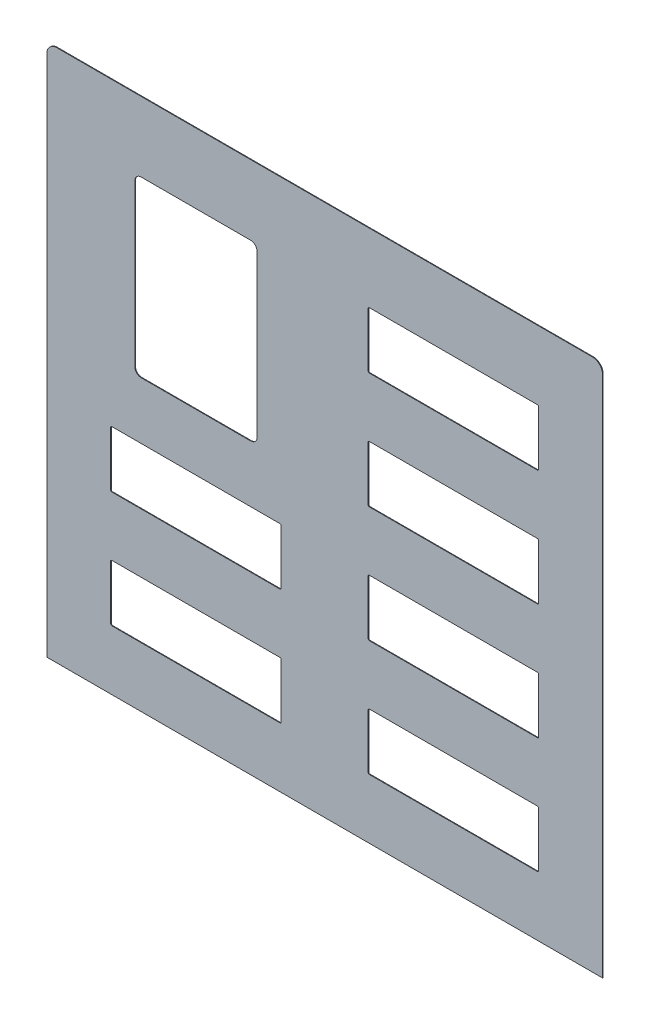
SolidWorks part; units mm, degrees
ref_plane "Front Plane" through (0, 0, 0) normal (0, 0, 1) x (1, 0, 0)
ref_plane "Top Plane" through (0, 0, 0) normal (0, 1, 0) x (1, 0, 0)
ref_plane "Right Plane" through (0, 0, 0) normal (1, 0, 0) x (0, 0, -1)
sketch "Sketch1" plane through (0, 0, 0) normal (0, 0, 1) x (1, 0, 0)
  line L1 (0, 0) -> (863.4, 0)
  line L2 (0, 0) -> (0, 812)
  line L3 (15.7, 827.7) -> (847.7, 827.7)
  line L4 (863.4, 0) -> (863.4, 812)
  arc A0 (847.7, 827.7) -> (863.4, 812) centre (847.7, 812) cw
  arc A1 (0, 812) -> (15.7, 827.7) centre (15.7, 812) cw
  dimension "D3" = 15.7
  dimension "D1" = 863.4
  dimension "D2" = 827.7
base flange "Base-Flange1" sketch "Sketch1" thickness 1 reverse thickness direction no parameters "D1"=1
edge flange "Edge-Flange1" [suppressed] sketch "Sketch8" flange angle 90 flange position material inside bend radius 1 thickness 1
sketch "Sketch8" plane through (0, 0, -1) normal (0, -1, 0) x (-1, 0, 0)
  line L0 (0, 0) -> (-822, 0) construction
  line L1 (-42, 0) -> (-780, 0)
  line L2 (-780, 0) -> (-780, 12)
  line L3 (-780, 12) -> (-42, 12)
  line L4 (-42, 12) -> (-42, 0)
  line L5 (0, 0) -> (0, -1) construction
  line L6 (-822, 0) -> (-822, -1) construction
  circle A0 centre (-81, 6) radius 2.75
  circle A1 centre (-261, 6) radius 2.75
  circle A2 centre (-441, 6) radius 2.75
  circle A3 centre (-621, 6) radius 2.75
  circle A4 centre (-801, 6) radius 2.75
  circle A5 centre (-981, 6) radius 2.75
  circle A6 centre (-1161, 6) radius 2.75
  point P6 (-42, 6)
  dimension "D1" = 5.5
  dimension "D2" = 39
  dimension "D4" = 42
  dimension "D5" = 42
  dimension "D3" = 7
bend "EdgeBend1" bend radius 1 bend angle 90 parameters "D5"=1, "D6"=10, "D7"=12
sketch "Sketch9" plane through (0, 0, 0) normal (0, 0, 1) x (1, 0, 0)
  line L0 (863.4, 0) -> (863.4, 812) construction
  line L1 (762.2, 720.7) -> (501.2, 720.7)
  line L2 (764.2, 718.7) -> (764.2, 634.7)
  line L3 (762.2, 632.7) -> (501.2, 632.7)
  line L4 (499.2, 718.7) -> (499.2, 634.7)
  line L5 (847.7, 827.7) -> (15.7, 827.7) construction
  line L38 (764.2, 538.7) -> (764.2, 454.7)
  line L39 (762.2, 540.7) -> (501.2, 540.7)
  line L40 (762.2, 452.7) -> (501.2, 452.7)
  line L41 (499.2, 538.7) -> (499.2, 454.7)
  line L42 (764.2, 358.7) -> (764.2, 274.7)
  line L43 (762.2, 360.7) -> (501.2, 360.7)
  line L44 (762.2, 272.7) -> (501.2, 272.7)
  line L45 (499.2, 358.7) -> (499.2, 274.7)
  line L46 (764.2, 178.7) -> (764.2, 94.7)
  line L47 (762.2, 180.7) -> (501.2, 180.7)
  line L48 (762.2, 92.7) -> (501.2, 92.7)
  line L49 (499.2, 178.7) -> (499.2, 94.7)
  line L58 (364.2, 358.7) -> (364.2, 274.7)
  line L59 (362.2, 360.7) -> (101.2, 360.7)
  line L60 (362.2, 272.7) -> (101.2, 272.7)
  line L61 (99.2, 358.7) -> (99.2, 274.7)
  line L62 (364.2, 178.7) -> (364.2, 94.7)
  line L63 (362.2, 180.7) -> (101.2, 180.7)
  line L64 (362.2, 92.7) -> (101.2, 92.7)
  line L65 (99.2, 178.7) -> (99.2, 94.7)
  line L66 (364.2, 718.7) -> (364.2, 634.7) [skipped]
  line L67 (362.2, 720.7) -> (101.2, 720.7) [skipped]
  line L68 (362.2, 632.7) -> (101.2, 632.7) [skipped]
  line L69 (99.2, 718.7) -> (99.2, 634.7) [skipped]
  line L70 (364.2, 538.7) -> (364.2, 454.7) [skipped]
  line L71 (362.2, 540.7) -> (101.2, 540.7) [skipped]
  line L72 (362.2, 452.7) -> (101.2, 452.7) [skipped]
  line L73 (99.2, 538.7) -> (99.2, 454.7) [skipped]
  arc A0 (764.2, 634.7) -> (762.2, 632.7) centre (762.2, 634.7) cw
  arc A1 (501.2, 632.7) -> (499.2, 634.7) centre (501.2, 634.7) cw
  arc A2 (501.2, 720.7) -> (499.2, 718.7) centre (501.2, 718.7) ccw
  arc A3 (762.2, 720.7) -> (764.2, 718.7) centre (762.2, 718.7) cw
  arc A36 (762.2, 540.7) -> (764.2, 538.7) centre (762.2, 538.7) cw
  arc A37 (764.2, 454.7) -> (762.2, 452.7) centre (762.2, 454.7) cw
  arc A38 (501.2, 452.7) -> (499.2, 454.7) centre (501.2, 454.7) cw
  arc A39 (501.2, 540.7) -> (499.2, 538.7) centre (501.2, 538.7) ccw
  arc A40 (762.2, 360.7) -> (764.2, 358.7) centre (762.2, 358.7) cw
  arc A41 (764.2, 274.7) -> (762.2, 272.7) centre (762.2, 274.7) cw
  arc A42 (501.2, 272.7) -> (499.2, 274.7) centre (501.2, 274.7) cw
  arc A43 (501.2, 360.7) -> (499.2, 358.7) centre (501.2, 358.7) ccw
  arc A44 (762.2, 180.7) -> (764.2, 178.7) centre (762.2, 178.7) cw
  arc A45 (764.2, 94.7) -> (762.2, 92.7) centre (762.2, 94.7) cw
  arc A46 (501.2, 92.7) -> (499.2, 94.7) centre (501.2, 94.7) cw
  arc A47 (501.2, 180.7) -> (499.2, 178.7) centre (501.2, 178.7) ccw
  arc A56 (362.2, 360.7) -> (364.2, 358.7) centre (362.2, 358.7) cw
  arc A57 (364.2, 274.7) -> (362.2, 272.7) centre (362.2, 274.7) cw
  arc A58 (101.2, 272.7) -> (99.2, 274.7) centre (101.2, 274.7) cw
  arc A59 (101.2, 360.7) -> (99.2, 358.7) centre (101.2, 358.7) ccw
  arc A60 (362.2, 180.7) -> (364.2, 178.7) centre (362.2, 178.7) cw
  arc A61 (364.2, 94.7) -> (362.2, 92.7) centre (362.2, 94.7) cw
  arc A62 (101.2, 92.7) -> (99.2, 94.7) centre (101.2, 94.7) cw
  arc A63 (101.2, 180.7) -> (99.2, 178.7) centre (101.2, 178.7) ccw
  arc A64 (362.2, 720.7) -> (364.2, 718.7) centre (362.2, 718.7) cw [skipped]
  arc A65 (364.2, 634.7) -> (362.2, 632.7) centre (362.2, 634.7) cw [skipped]
  arc A66 (101.2, 632.7) -> (99.2, 634.7) centre (101.2, 634.7) cw [skipped]
  arc A67 (101.2, 720.7) -> (99.2, 718.7) centre (101.2, 718.7) ccw [skipped]
  arc A68 (362.2, 540.7) -> (364.2, 538.7) centre (362.2, 538.7) cw [skipped]
  arc A69 (364.2, 454.7) -> (362.2, 452.7) centre (362.2, 454.7) cw [skipped]
  arc A70 (101.2, 452.7) -> (99.2, 454.7) centre (101.2, 454.7) cw [skipped]
  arc A71 (101.2, 540.7) -> (99.2, 538.7) centre (101.2, 538.7) ccw [skipped]
  dimension "D5" = 2
  dimension "D1" = 99.2
  dimension "D2" = 265
  dimension "D3" = 88
  dimension "D4" = 107
  dimension "D6" = 2
  dimension "D7" = 4
extrude "Cut-Extrude1" cut sketch "Sketch9" against normal blind 10 normal cut yes
sketch "Sketch10" plane through (0, 0, 0) normal (0, 0, 1) x (1, 0, 0)
  line L1 (146.7, 449.2) -> (316.7, 449.2)
  line L2 (136.7, 459.2) -> (136.7, 709.2)
  line L3 (146.7, 719.2) -> (316.7, 719.2)
  line L4 (326.7, 459.2) -> (326.7, 709.2)
  line L6 (863.4, 0) -> (863.4, 812) construction
  line L8 (847.7, 827.7) -> (15.7, 827.7) construction
  arc A0 (146.7, 449.2) -> (136.7, 459.2) centre (146.7, 459.2) cw
  arc A1 (316.7, 449.2) -> (326.7, 459.2) centre (316.7, 459.2) ccw
  arc A2 (136.7, 709.2) -> (146.7, 719.2) centre (146.7, 709.2) cw
  arc A3 (316.7, 719.2) -> (326.7, 709.2) centre (316.7, 709.2) cw
  dimension "D5" = 10
  dimension "D1" = 190
  dimension "D2" = 270
  dimension "D3" = 108.5
  dimension "D4" = 536.7
extrude "Cut-Extrude2" cut sketch "Sketch10" against normal blind 10 normal cut yes
sketch "Bend-Lines1" [suppressed] plane through (0, 0, 0) normal (0, 1, 0) x (1, 0, 0)
sketch "Bounding-Box1" [suppressed] plane through (0, 0, 0) normal (0, 1, 0) x (1, 0, 0)
sheet metal parameters "Sheet-Metal1" thickness 1 parameters "D1"=2
flat pattern "Flat-Pattern1" [suppressed]
sketch "Bend-Lines2" plane through (0, 0, 0) normal (0, 1, 0) x (1, 0, 0)
sketch3d "Bounding-Box2" [suppressed]
  line L0 (15, 15, 0) -> (-1227, 15, 0) construction
  line L1 (15, -935, 0) -> (-1227, -935, 0) construction
  line L2 (15, 15, 0) -> (15, -935, 0) construction
  line L3 (-1227, 15, 0) -> (-1227, -935, 0) construction
sheet metal parameters "Sheet-Metal2" thickness 1 parameters "D1"=2
flat pattern "Flat-Pattern1"
sketch "Bend-Lines2" plane through (0, 0, 0) normal (0, 0, 1) x (1, 0, 0)
  line L0 (0, 0.8219) -> (1242, 0.8219) construction
  line L1 (0, 0.8219) -> (1242, 0.8219) construction
sketch3d "Bounding-Box2" [suppressed]
  line L0 (-15, 15, 0) -> (1227, 15, 0) construction
  line L1 (-15, -946.3562, 0) -> (1227, -946.3562, 0) construction
  line L2 (-15, 15, 0) -> (-15, -946.3562, 0) construction
  line L3 (1227, 15, 0) -> (1227, -946.3562, 0) construction
bend of the flat pattern "Flatten-<EdgeBend1>1"
sheet metal parameters "Sheet-Metal3" thickness 1 parameters "D1"=2
flat pattern "Flat-Pattern1"
sketch "Bend-Lines2" plane through (0, 0, 0) normal (0, 0, 1) x (1, 0, 0)
  line L0 (0, 0.8219) -> (1244, 0.8219) construction
  line L1 (0, 0.8219) -> (1244, 0.8219) construction
sketch3d "Bounding-Box2" [suppressed]
  line L0 (-16, 16, 0) -> (1228, 16, 0) construction
  line L1 (-16, -945.3562, 0) -> (1228, -945.3562, 0) construction
  line L2 (-16, 16, 0) -> (-16, -945.3562, 0) construction
  line L3 (1228, 16, 0) -> (1228, -945.3562, 0) construction
sheet metal parameters "Sheet-Metal4" thickness 1 parameters "D1"=2
flat pattern "Flat-Pattern1"
sketch "Bend-Lines2" plane through (0, 0, 0) normal (0, 0, 1) x (1, 0, 0)
sketch3d "Bounding-Box2" [suppressed]
  line L0 (-15.7, 15.7, 0) -> (807.7, 15.7, 0) construction
  line L1 (-15.7, -792.7, 0) -> (807.7, -792.7, 0) construction
  line L2 (-15.7, 15.7, 0) -> (-15.7, -792.7, 0) construction
  line L3 (807.7, 15.7, 0) -> (807.7, -792.7, 0) construction
equation "\"D5@Sketch8\"=\"D4@Sketch8\""
